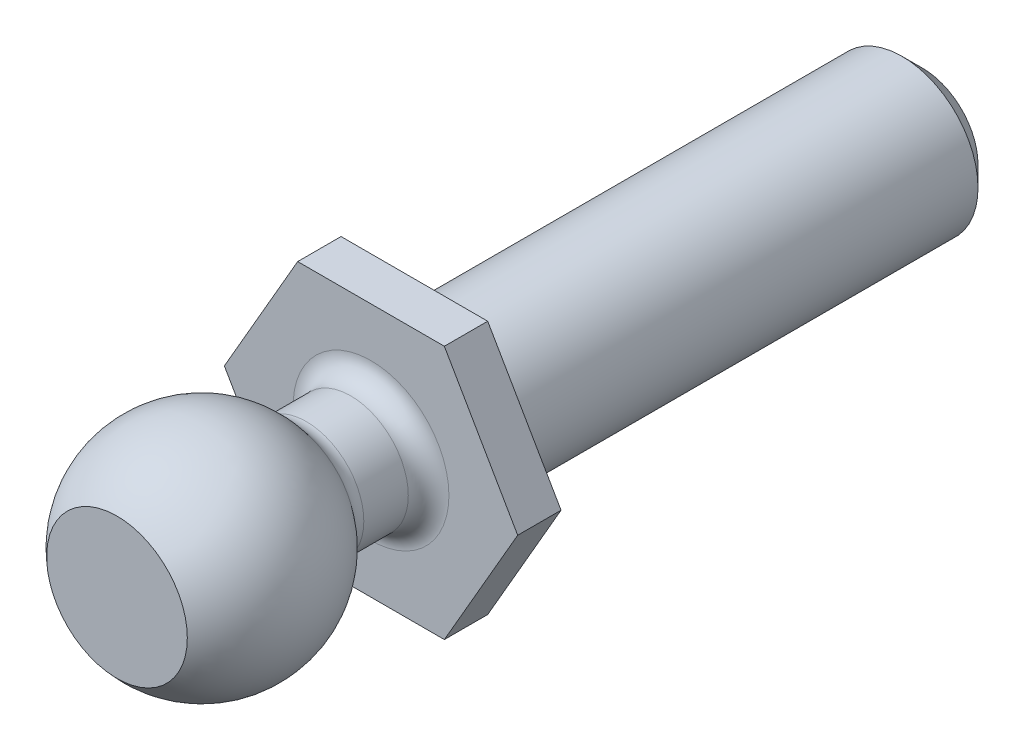
SolidWorks part; units mm, degrees
material "Alloy Steel"
ref_plane "Front Plane" through (0, 0, 0) normal (0, 0, 1) x (1, 0, 0)
ref_plane "Top Plane" through (0, 0, 0) normal (0, 1, 0) x (1, 0, 0)
ref_plane "Right Plane" through (0, 0, 0) normal (1, 0, 0) x (0, 0, -1)
sketch "Sketch1" plane through (0, 0, 0) normal (0, 0, 1) x (1, 0, 0)
  line L1 (1.3748, -2.3812) -> (2.7496, 0)
  line L2 (2.7496, 0) -> (1.3748, 2.3812)
  line L3 (1.3748, 2.3812) -> (-1.3748, 2.3812)
  line L4 (-1.3748, 2.3812) -> (-2.7496, 0)
  line L5 (-2.7496, 0) -> (-1.3748, -2.3813)
  line L6 (-1.3748, -2.3813) -> (1.3748, -2.3812)
  circle A0 centre (0, 0) radius 2.3813 construction
  dimension "D1" = 4.7625
extrude "Boss-Extrude1" add sketch "Sketch1" along normal blind 0.8128
sketch "Sketch2" plane through (0, 0, 0.8128) normal (0, 0, 1) x (1, 0, 0)
  circle A0 centre (0, 0) radius 1.0795
  dimension "D1" = 2.159
extrude "Boss-Extrude2" add sketch "Sketch2" along normal blind 3.175
sketch "Sketch3" plane through (0, 0, 3.9878) normal (0, 0, 1) x (1, 0, 0)
  line L0 (0, -1000) -> (0, 49000) construction
  circle A0 centre (0, 0) radius 2.0638
  dimension "D1" = 4.1275
revolve "Revolve2" add sketch "Sketch3" angle 360 about L0
fillet "Fillet1" radius 0.381 2 edges at (1.0795, 0, 2.2289) (1.0795, 0, 0.8128)
sketch "Sketch4" plane through (0, 0, 0) normal (0, 0, -1) x (-1, 0, 0)
  circle A0 centre (0, 0) radius 1.4224
  dimension "D1" = 2.8448
extrude "Boss-Extrude3" add sketch "Sketch4" along normal blind 9.525
cosmetic thread "Cosmetic Thread1" parameters "D2"=2.0879
chamfer "Chamfer1" distance 0.381 angle 45 1 edges at (-1.4224, 0, -9.525)
ref_plane "Plane1" through (0, 0, 5.5753) normal (0, 0, 1) x (1, 0, 0)
split "Split1" trim tools "Plane1" bodies to split 104 resulting bodies 105
